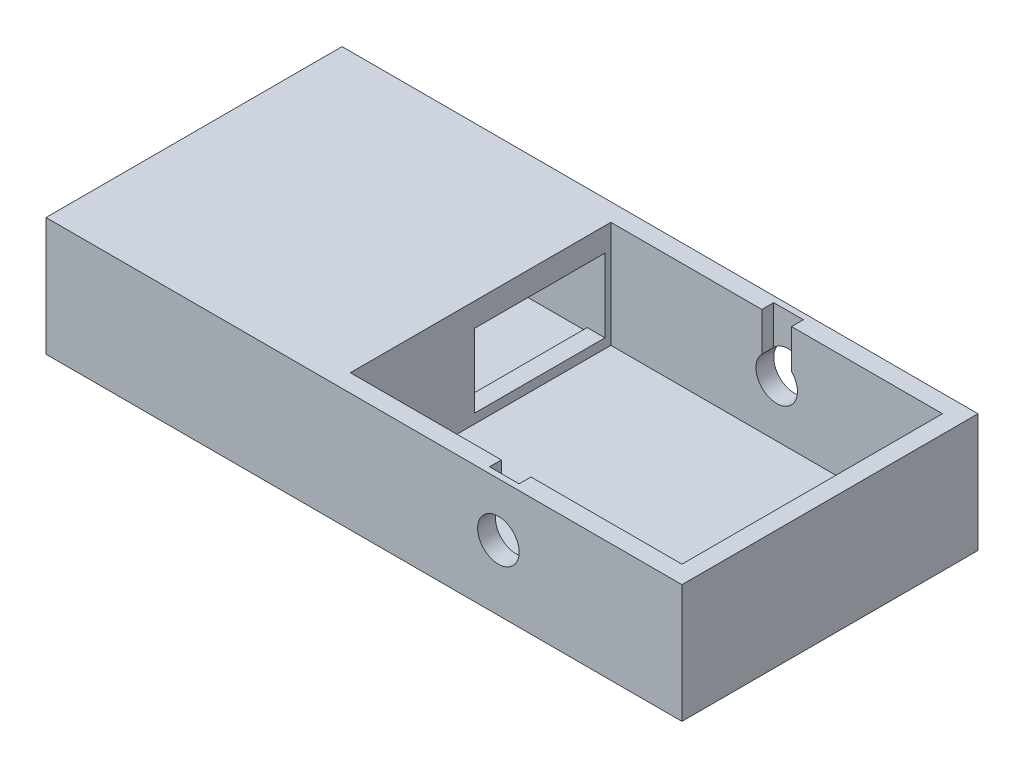
SolidWorks part; units mm, degrees
ref_plane "Front" through (0, 0, 0) normal (0, 0, 1) x (1, 0, 0)
ref_plane "Top" through (0, 0, 0) normal (0, 1, 0) x (1, 0, 0)
ref_plane "Right" through (0, 0, 0) normal (1, 0, 0) x (0, 0, -1)
sketch "Sketch1" plane through (0, 0, 0) normal (0, 1, 0) x (1, 0, 0)
  line L1 (-39.37, 31.75) -> (39.37, 31.75)
  line L2 (-39.37, 31.75) -> (-39.37, -31.75)
  line L3 (-39.37, -31.75) -> (39.37, -31.75)
  line L4 (39.37, 31.75) -> (39.37, -31.75)
  line L5 (-39.37, 31.75) -> (39.37, -31.75) construction
  line L6 (-39.37, -31.75) -> (39.37, 31.75) construction
  line L7 (-35.56, 27.94) -> (35.56, 27.94)
  line L8 (-35.56, 27.94) -> (-35.56, -27.94)
  line L9 (-35.56, -27.94) -> (35.56, -27.94)
  line L10 (35.56, 27.94) -> (35.56, -27.94)
  line L11 (-35.56, 27.94) -> (35.56, -27.94) construction
  line L12 (-35.56, -27.94) -> (35.56, 27.94) construction
  point P0 (0, 0)
  point P6 (0, 0)
  dimension "D1" = 63.5
  dimension "D2" = 78.74
  dimension "D3" = 55.88
  dimension "D4" = 71.12
extrude "pcb-base" add sketch "Sketch1" along normal blind 2.54 contours L8 L7 L10 L9
extrude "pcb-wall" add sketch "Sketch1<4>" along normal blind 25.4
sketch "Sketch1<4>" plane through (0, 0, 0) normal (0, 1, 0) x (1, 0, 0) same geometry as "Sketch1"
sketch "Sketch2" plane through (-39.37, 0, 0) normal (-1, 0, 0) x (0, 0, 1)
  line L0 (-31.75, 25.4) -> (31.75, 25.4) construction
  line L1 (-26.67, 4.572) -> (1.27, 4.572)
  line L2 (-26.67, 4.572) -> (-26.67, 20.32)
  line L3 (-26.67, 20.32) -> (1.27, 20.32)
  line L4 (1.27, 4.572) -> (1.27, 20.32)
  line L5 (-26.67, 4.572) -> (1.27, 20.32) construction
  line L6 (-26.67, 20.32) -> (1.27, 4.572) construction
  line L7 (31.75, 25.4) -> (31.75, 0) construction
  line L8 (-31.75, 25.4) -> (-31.75, 0) construction
  line L9 (-31.75, 0) -> (31.75, 0) construction
  point P0 (-12.7, 12.446)
  dimension "D1" = 5.08
  dimension "0.35" = 30.48
  dimension "D3" = 5.08
  dimension "0.175" = 4.572
extrude "pcb-gap" cut sketch "Sketch2" against normal up to vertex (3.81 mm away) up to point (-35.56, 25.4, 27.94)
sketch "Sketch3" plane through (0, 0, -27.94) normal (0, 0, 1) x (1, 0, 0)
  line L0 (-35.56, 25.4) -> (-35.56, 2.54) construction
  line L2 (-3.175, 13.97) -> (3.175, 13.97)
  line L3 (35.56, 25.4) -> (-35.56, 25.4) construction
  line L4 (-3.175, 13.97) -> (-3.175, 25.4)
  line L5 (-3.175, 25.4) -> (3.175, 25.4)
  line L6 (3.175, 13.97) -> (3.175, 25.4)
  line L7 (-3.175, 13.97) -> (3.175, 25.4) construction
  line L8 (-3.175, 25.4) -> (3.175, 13.97) construction
  circle A0 centre (0, 13.97) radius 4.445
  point P7 (0, 19.685)
  line M4 (35.56, 25.4) -> (-35.56, 25.4)
  dimension "D2" = 8.89
  dimension "D1" = 35.56
  dimension "D3" = 11.43
  dimension "D4" = 6.35
sketch "Sketch4" plane through (0, 0, 27.94) normal (0, 0, -1) x (-1, 0, 0)
  line L0 (35.56, 25.4) -> (-35.56, 25.4) construction
  line L1 (-3.175, 25.4) -> (3.175, 25.4)
  line L2 (-3.175, 25.4) -> (-3.175, 13.97)
  line L3 (-3.175, 13.97) -> (3.175, 13.97)
  line L4 (3.175, 25.4) -> (3.175, 13.97)
  line L5 (-3.175, 25.4) -> (3.175, 13.97) construction
  line L6 (-3.175, 13.97) -> (3.175, 25.4) construction
  circle A0 centre (0, 13.97) radius 4.445
  point P2 (0, 19.685)
  line M4 (35.56, 25.4) -> (-35.56, 25.4)
  dimension "D1" = 8.89
  dimension "D2" = 6.35
  dimension "D3" = 3.175
extrude "lid-hole-1" cut sketch "Sketch4" against normal blind 3.81 contours L2 A0 L4 L3 | L4 A0 L2 L3 region at (0, 16.004, 27.94) region at (0, 12.5426, 27.94)
extrude "hole-slide-1" cut sketch "Sketch4<6>" against normal blind 2.54 contours A0 L4 L2 M4 region at (0, 21.6904, 27.94)
sketch "Sketch4<6>" plane through (0, 0, 27.94) normal (0, 0, -1) x (-1, 0, 0) same geometry as "Sketch4"
extrude "lid-hole-2" cut sketch "Sketch3" against normal blind 3.81 contours L4 A0 L6 L2 | L6 A0 L4 L2 region at (0, 16.004, -27.94) region at (0, 12.5426, -27.94)
extrude "hole-slide-2" cut sketch "Sketch3<5>" against normal blind 2.54 contours A0 L6 L4 M4 region at (0, 21.6904, -27.94)
sketch "Sketch3<5>" plane through (0, 0, -27.94) normal (0, 0, 1) x (1, 0, 0) same geometry as "Sketch3"
sketch "Sketch5" plane through (-39.37, 0, 0) normal (-1, 0, 0) x (0, 0, 1)
  line L0 (31.75, 25.4) -> (31.75, 0) construction
  line L1 (-31.75, 0) -> (31.75, 0)
  line L2 (-31.75, 0) -> (-31.75, 3.81)
  line L3 (-31.75, 3.81) -> (31.75, 3.81)
  line L4 (31.75, 0) -> (31.75, 3.81)
  line L5 (1.27, 20.32) -> (-26.67, 20.32) construction
  line L6 (-31.75, 25.4) -> (31.75, 25.4) construction
  line L7 (-31.75, 0) -> (6.35, 0)
  line L8 (-31.75, 0) -> (-31.75, 3.81)
  line L9 (-31.75, 3.81) -> (6.35, 3.81)
  line L10 (6.35, 0) -> (6.35, 3.81)
  line L11 (-31.75, 3.81) -> (-26.67, 3.81)
  line L12 (-31.75, 3.81) -> (-31.75, 25.4)
  line L13 (-31.75, 25.4) -> (-26.67, 25.4)
  line L14 (-26.67, 3.81) -> (-26.67, 25.4)
  line L15 (6.35, 3.81) -> (1.27, 3.81)
  line L16 (6.35, 3.81) -> (6.35, 25.4)
  line L17 (6.35, 25.4) -> (1.27, 25.4)
  line L18 (1.27, 3.81) -> (1.27, 25.4)
  line L19 (-26.67, 25.4) -> (1.27, 25.4)
  line L20 (-26.67, 25.4) -> (-26.67, 20.32)
  line L21 (-26.67, 20.32) -> (1.27, 20.32)
  line L22 (1.27, 25.4) -> (1.27, 20.32)
  line M13 (-26.67, 20.32) -> (1.27, 20.32)
  line M14 (1.27, 20.32) -> (1.27, 4.572)
  line M16 (-26.67, 4.572) -> (-26.67, 20.32)
  line M17 (-31.75, 0) -> (31.75, 0)
  line M19 (31.75, 25.4) -> (-31.75, 25.4)
  line M20 (-31.75, 25.4) -> (-31.75, 0)
  dimension "D1" = 3.81
  dimension "D2" = 38.1
  dimension "D3" = 5.08
  dimension "D4" = 5.08
extrude "Boss-Extrude3" add sketch "Sketch5" along normal blind 48.768 contours L3 L14 M16 M19 M20 | L18 L14 M13 M19 | L18 L3 L16 M19 M14 | L10 L3 L9 M17 M20 region at (-39.37, 1.905, -12.7) region at (-39.37, 14.605, -29.21) region at (-39.37, 14.605, 3.81) region at (-39.37, 22.86, -12.7)
sketch "Sketch7" plane through (-88.138, 0, 0) normal (-1, 0, 0) x (0, 0, 1)
  line L1 (-31.75, 25.4) -> (6.35, 25.4)
  line L2 (-31.75, 25.4) -> (-31.75, 0)
  line L3 (-31.75, 0) -> (6.35, 0)
  line L4 (6.35, 25.4) -> (6.35, 0)
extrude "Boss-Extrude4" add sketch "Sketch7" along normal blind 8.89 and the other way blind 1.27
sketch "Sketch8" plane through (0, 0, 6.35) normal (0, 0, 1) x (1, 0, 0)
  line L0 (-97.028, 0) -> (-39.37, 0) construction
  line L1 (-97.028, 25.4) -> (-94.488, 25.4)
  line L2 (-97.028, 25.4) -> (-97.028, 0)
  line L3 (-97.028, 0) -> (-94.488, 0)
  line L4 (-94.488, 25.4) -> (-94.488, 0)
  line L5 (-39.37, 0) -> (-39.37, 25.4) construction
  line L6 (-97.028, 25.4) -> (-39.37, 25.4)
  line L7 (-97.028, 25.4) -> (-97.028, 22.86)
  line L8 (-97.028, 22.86) -> (-39.37, 22.86)
  line L9 (-39.37, 25.4) -> (-39.37, 22.86)
  line L15 (-97.028, 0) -> (-39.37, 0)
  line L16 (-97.028, 0) -> (-97.028, 2.54)
  line L17 (-97.028, 2.54) -> (-39.37, 2.54)
  line L18 (-39.37, 0) -> (-39.37, 2.54)
  line M10 (-97.028, 0) -> (-39.37, 0)
  line M11 (-39.37, 0) -> (-39.37, 25.4)
  dimension "D1" = 2.54
  dimension "D3" = 2.54
  dimension "D4" = 2.54
extrude "Boss-Extrude5" add sketch "Sketch8" along normal blind 25.4 contours L2 L17 L4 L8 | L17 L4 M10 M11 | L2 L1 L4 L3 | L7 L8 L9 L6 region at (-95.758, 12.7, 6.35) region at (-66.929, 1.27, 6.35)
sketch "Sketch9" plane through (0, 0, 31.75) normal (0, 0, 1) x (1, 0, 0)
  line L0 (-97.028, 0) -> (39.37, 0) construction
  line L1 (-97.028, 25.4) -> (-39.37, 25.4)
  line L2 (-97.028, 25.4) -> (-97.028, 0)
  line L3 (-97.028, 0) -> (-39.37, 0)
  line L4 (-39.37, 25.4) -> (-39.37, 0)
extrude "Boss-Extrude6" add sketch "Sketch9" against normal blind 3.81
